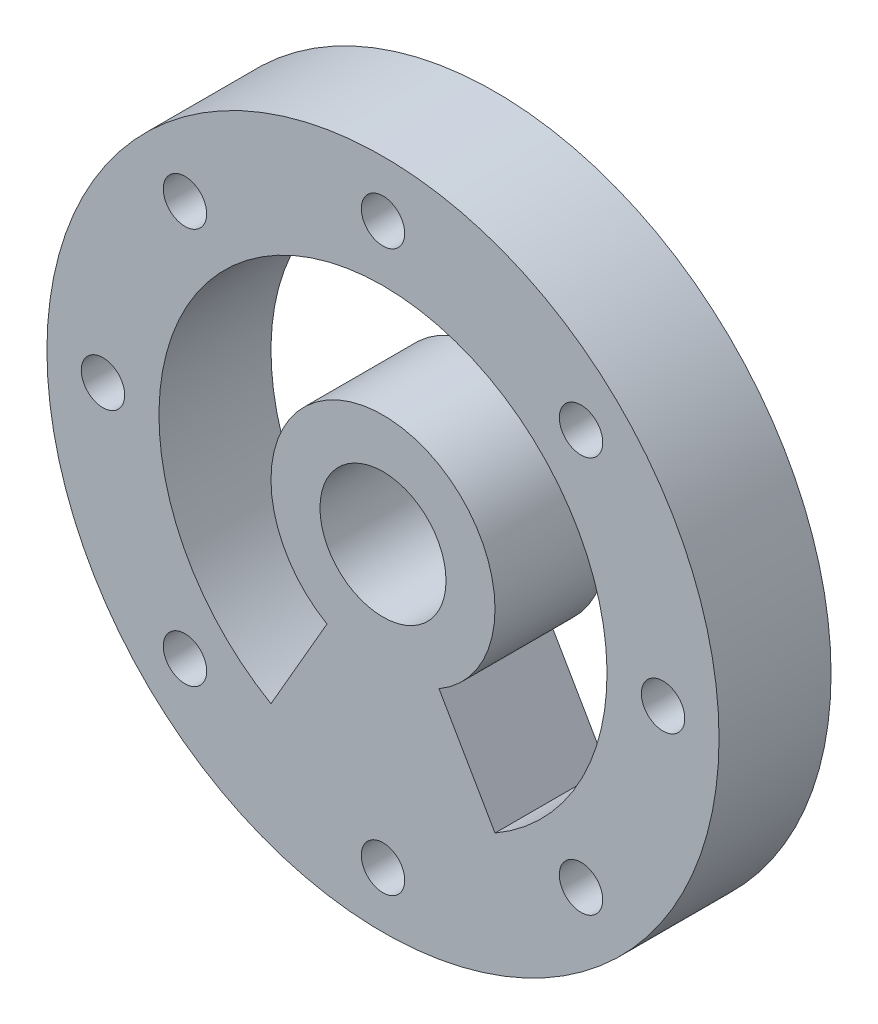
SolidWorks part; units mm, degrees
ref_plane "Front Plane" through (0, 0, 0) normal (0, 0, 1) x (1, 0, 0)
ref_plane "Top Plane" through (0, 0, 0) normal (0, 1, 0) x (1, 0, 0)
ref_plane "Right Plane" through (0, 0, 0) normal (1, 0, 0) x (0, 0, -1)
ref_axis "Axis1" through (0, 0, 5.5) along (0, 0, -1)
sketch "Sketch4" plane through (0, 0, 0) normal (0, 0, 1) x (1, 0, 0)
  line L0 (0, 0) -> (-9.5, -16.4545) construction
  line L1 (0, 0) -> (9.5, -16.4545) construction
  line L2 (-4, -6.9282) -> (-8, -13.8564)
  line L3 (4, -6.9282) -> (8, -13.8564)
  arc A1 (8, -13.8564) -> (-8, -13.8564) centre (0, 0) ccw
  arc A2 (4, -6.9282) -> (-4, -6.9282) centre (0, 0) ccw
sketch "Sketch6" plane through (0, 0, 0) normal (0, 0, 1) x (1, 0, 0)
  circle A0 centre (0, 0) radius 24
extrude "Boss-Extrude1" add sketch "Sketch6" along normal blind 8
extrude "Cut-Extrude4" cut sketch "Sketch4" along normal blind 8
sketch "Sketch7" plane through (0, 0, 0) normal (0, 0, -1) x (-1, 0, 0)
  circle A0 centre (0, 0) radius 4.5
extrude "Cut-Extrude5" cut sketch "Sketch7" against normal up to surface (8 mm away) up to face at (24, 0, 8)
sketch "Sketch8" plane through (0, 0, 0) normal (0, 0, -1) x (-1, 0, 0)
  line L0 (0, 0) -> (0, 20) construction
  circle A0 centre (0, 20) radius 1.55
  circle A1 centre (14.1421, 14.1421) radius 1.55
  circle A2 centre (20, 0) radius 1.55
  circle A3 centre (14.1421, -14.1421) radius 1.55
  circle A4 centre (0, -20) radius 1.55
  circle A5 centre (-14.1421, -14.1421) radius 1.55
  circle A6 centre (-20, 0) radius 1.55
  circle A7 centre (-14.1421, 14.1421) radius 1.55
  point P20 (0, 0)
  dimension "D1" = 8
extrude "Cut-Extrude6" cut sketch "Sketch8" against normal up to surface (8 mm away) up to face at (4.5, 0, 8)
